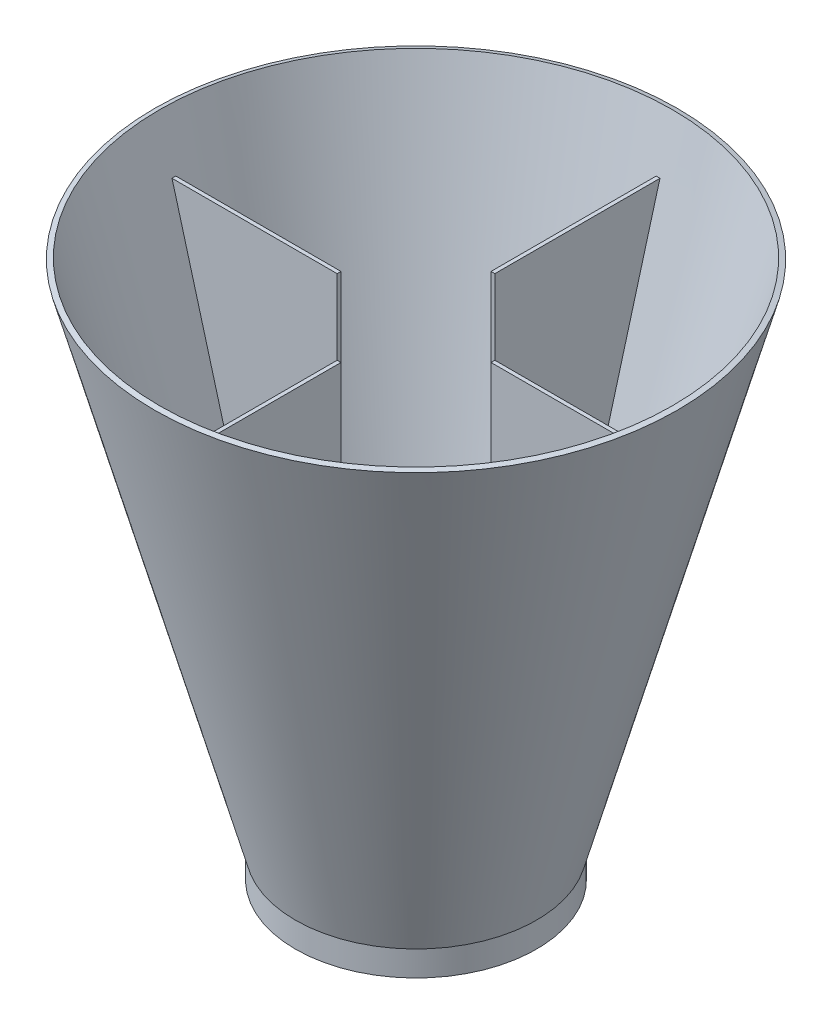
SolidWorks part; units mm, degrees
ref_plane "Front Plane" through (0, 0, 0) normal (0, 0, 1) x (1, 0, 0)
ref_plane "Top Plane" through (0, 0, 0) normal (0, 1, 0) x (1, 0, 0)
ref_plane "Right Plane" through (0, 0, 0) normal (1, 0, 0) x (0, 0, -1)
sketch "Sketch1" plane through (0, 0, 0) normal (1, 0, 0) x (0, 0, -1)
  line L2 (0, 0) -> (0, 32.4616) construction
  line L8 (100, 200) -> (45, 0)
  dimension "D3" = 45
revolve "Revolve-Thin1" add sketch "Sketch1" angle 360 about L2 wall 2
sketch "Sketch2" plane through (0, 0, 0) normal (0, 1, 0) x (1, 0, 0)
  circle A0 centre (0, 0) radius 13.35
  circle A1 centre (0, 0) radius 47.0175
extrude "Boss-Extrude1" add sketch "Sketch2" against normal blind 10
sketch "Sketch3" plane through (0, 0, 0) normal (1, 0, 0) x (0, 0, -1)
  line L2 (30, 180) -> (30, 30)
  line L3 (30, 30) -> (53.25, 30)
  line L4 (30, 180) -> (94.5, 180)
  line L5 (94.5, 180) -> (53.25, 30)
  dimension "D1" = 150
extrude "Boss-Extrude2" add sketch "Sketch3" along normal blind 0.75 and the other way blind 0.75 separate body
pattern_circular "CirPattern3" count 4 every 90 about axis through (0, 200, 0) along (0, -1, 0) of bodies 104
ref_plane "Plane1" through (0, 100, 0) normal (0, 1, 0) x (1, 0, 0)
